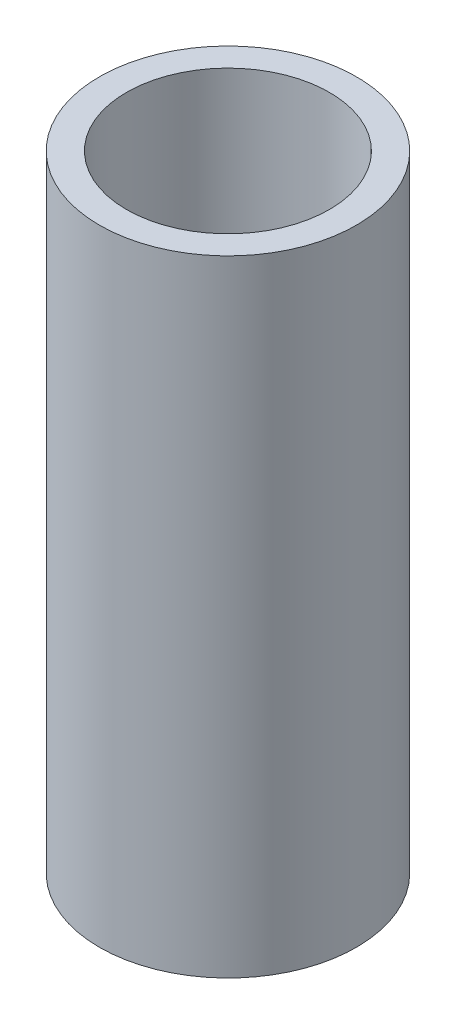
SolidWorks part; units mm, degrees
ref_plane "Front Plane" through (0, 0, 0) normal (0, 0, 1) x (1, 0, 0)
ref_plane "Top Plane" through (0, 0, 0) normal (0, 1, 0) x (1, 0, 0)
ref_plane "Right Plane" through (0, 0, 0) normal (1, 0, 0) x (0, 0, -1)
sketch "Sketch1" plane through (0, 0, 0) normal (0, 1, 0) x (1, 0, 0)
  circle A0 centre (0, 0) radius 30
  dimension "SLEEVE_OD" = 60
extrude "Boss-Extrude1" add sketch "Sketch1" along normal blind 145.965
sketch "Sketch2" plane through (0, 0, 0) normal (0, 1, 0) x (1, 0, 0)
  circle A0 centre (0, 0) radius 23.6876
  dimension "BORE_D" = 47.3753
extrude "Cut-Extrude1" cut sketch "Sketch2" along normal through all
chamfer "Chamfer1" distance 3.2203 angle 45 rebuild error yes
